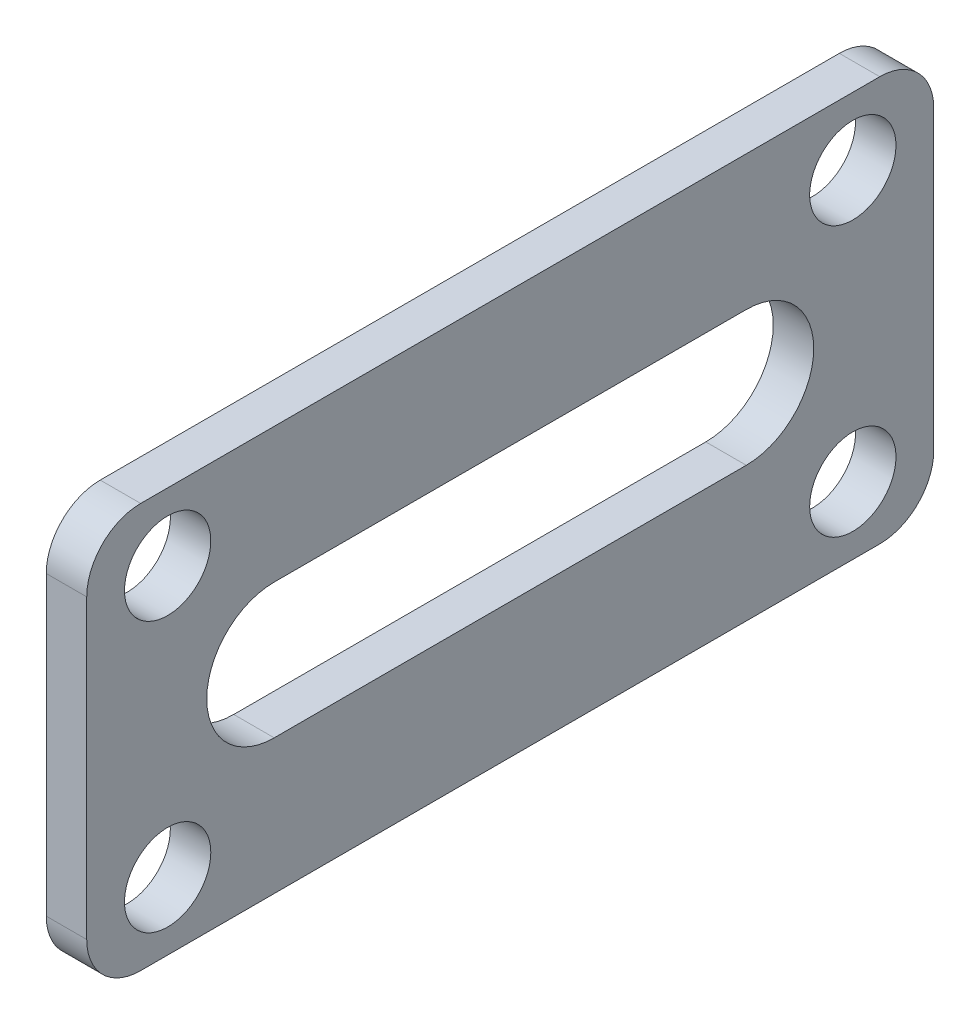
SolidWorks part; units mm, degrees
material "5052-H34"
ref_plane "正面" through (0, 0, 0) normal (0, 0, 1) x (1, 0, 0)
ref_plane "平面" through (0, 0, 0) normal (0, 1, 0) x (1, 0, 0)
ref_plane "右側面" through (0, 0, 0) normal (1, 0, 0) x (0, 0, -1)
sketch "ｽｹｯﾁ1" plane through (0, 0, 0) normal (1, 0, 0) x (0, 0, -1)
  line L0 (0, 5) -> (0, 0) construction
  line L1 (-12.7, 5) -> (12.7, 5) construction
  line L2 (-12.7, 5) -> (-12.7, -5) construction
  line L3 (-12.7, -5) -> (12.7, -5) construction
  line L4 (12.7, 5) -> (12.7, -5) construction
  line L5 (-12.7, 5) -> (12.7, -5) construction
  line L6 (-12.7, -5) -> (12.7, 5) construction
  line L7 (0, 0) -> (12.7, 0) construction
  line L8 (-8.75, 0) -> (8.75, 0) construction
  line L9 (-15.7, 7.5) -> (15.7, 7.5)
  line L10 (-15.7, 7.5) -> (-15.7, -7.5)
  line L11 (-15.7, -7.5) -> (15.7, -7.5)
  line L12 (15.7, 7.5) -> (15.7, -7.5)
  line L13 (-15.7, 7.5) -> (15.7, -7.5) construction
  line L14 (-15.7, -7.5) -> (15.7, 7.5) construction
  line L15 (-8.75, 2.5) -> (8.75, 2.5)
  line L16 (-8.75, -2.5) -> (8.75, -2.5)
  circle A0 centre (12.7, 5) radius 1.6
  circle A1 centre (12.7, -5) radius 1.6
  circle A2 centre (-12.7, 5) radius 1.6
  circle A3 centre (-12.7, -5) radius 1.6
  arc A4 (-8.75, 2.5) -> (-8.75, -2.5) centre (-8.75, 0) ccw
  arc A5 (8.75, -2.5) -> (8.75, 2.5) centre (8.75, 0) ccw
  point P0 (0, 0)
  point P19 (0, 0)
  dimension "D1" = 3.2
  dimension "D2" = 25.4
  dimension "D3" = 10
  dimension "D4" = 5
  dimension "D5" = 3
  dimension "D6" = 17.5
  dimension "D7" = 5
extrude "ﾎﾞｽ - 押し出し1" add sketch "ｽｹｯﾁ1" along normal blind 1.5
fillet "ﾌｨﾚｯﾄ1" radius 2 4 edges at (0.75, -7.5, -15.7) (0.75, 7.5, -15.7) (0.75, -7.5, 15.7) (0.75, 7.5, 15.7)
